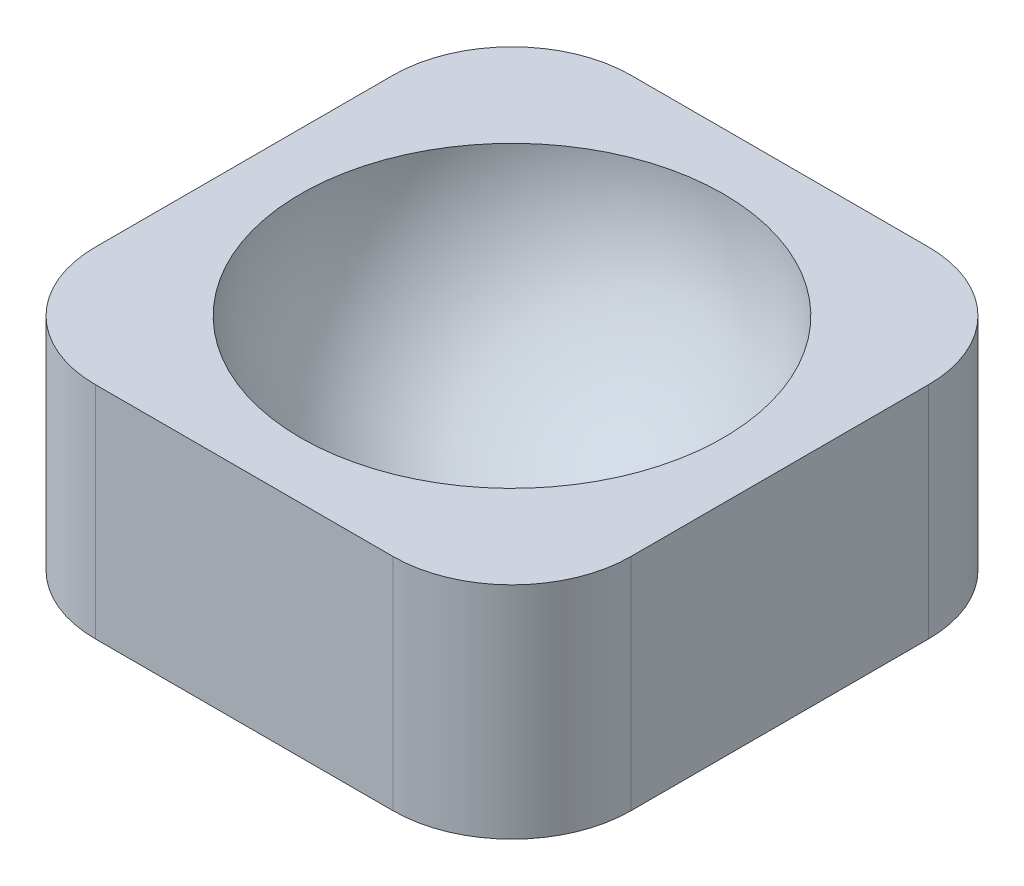
SolidWorks part; units mm, degrees
material "AISI 4340 Steel, normalized"
ref_plane "Front Plane" through (0, 0, 0) normal (0, 0, 1) x (1, 0, 0)
ref_plane "Top Plane" through (0, 0, 0) normal (0, 1, 0) x (1, 0, 0)
ref_plane "Right Plane" through (0, 0, 0) normal (1, 0, 0) x (0, 0, -1)
sketch "Sketch1" plane through (0, 0, 0) normal (0, 1, 0) x (1, 0, 0)
  line L1 (0, 0) -> (-114.3, 0)
  line L2 (0, 0) -> (0, 114.3)
  line L3 (0, 114.3) -> (-114.3, 114.3)
  line L4 (-114.3, 0) -> (-114.3, 114.3)
  circle A0 centre (-57.15, 57.15) radius 44.45
  point P7 (-101.6, 57.15)
  point P8 (-114.3, 57.15)
  point P9 (0, 57.15)
  point P10 (-57.15, 114.3)
  point P11 (-57.15, 0)
  point P13 (-57.15, 101.6)
  dimension "D1" = 88.9
  dimension "D2" = 12.7
  dimension "D3" = 12.7
extrude "Boss-Extrude1" add sketch "Sketch1" along normal blind 46.99 contours L4 L1 L2 L3 A0 | A0 region at (-57.15, 0, -1.6164) region at (-57.15, 0, -57.15)
sketch "Sketch2" plane through (0, 46.99, 0) normal (0, 1, 0) x (1, 0, 0)
  line L0 (-57.15, 114.3) -> (-57.15, 0) construction
  line L1 (0, 114.3) -> (-114.3, 114.3) construction
  line L2 (0, 0) -> (-114.3, 0) construction
  line L3 (-57.15, 102.235) -> (-57.15, 12.065)
  circle A0 centre (-57.15, 57.15) radius 45.085
  dimension "D1" = 90.17
revolve "Cut-Revolve1" cut sketch "Sketch2" angle 180 about L0 region at (-38.0153, 46.99, -57.15) reverse direction yes
fillet "Fillet1" radius 25.4 4 edges at (0, 23.495, 0) (-114.3, 23.495, 0) (-114.3, 23.495, -114.3) (0, 23.495, -114.3)
sketch "Sketch3" plane through (0, 0, 0) normal (0, -1, 0) x (1, 0, 0)
  line L0 (-57.15, -114.3) -> (-57.15, 0) construction
  line L1 (-25.4, -114.3) -> (-88.9, -114.3) construction
  line L2 (-25.4, 0) -> (-88.9, 0) construction
  line L3 (0, -57.15) -> (-114.3, -57.15) construction
  line L4 (0, -25.4) -> (0, -88.9) construction
  line L5 (-114.3, -25.4) -> (-114.3, -88.9) construction
equation "\"D3@Sketch1\"=\"D2@Sketch1\""
